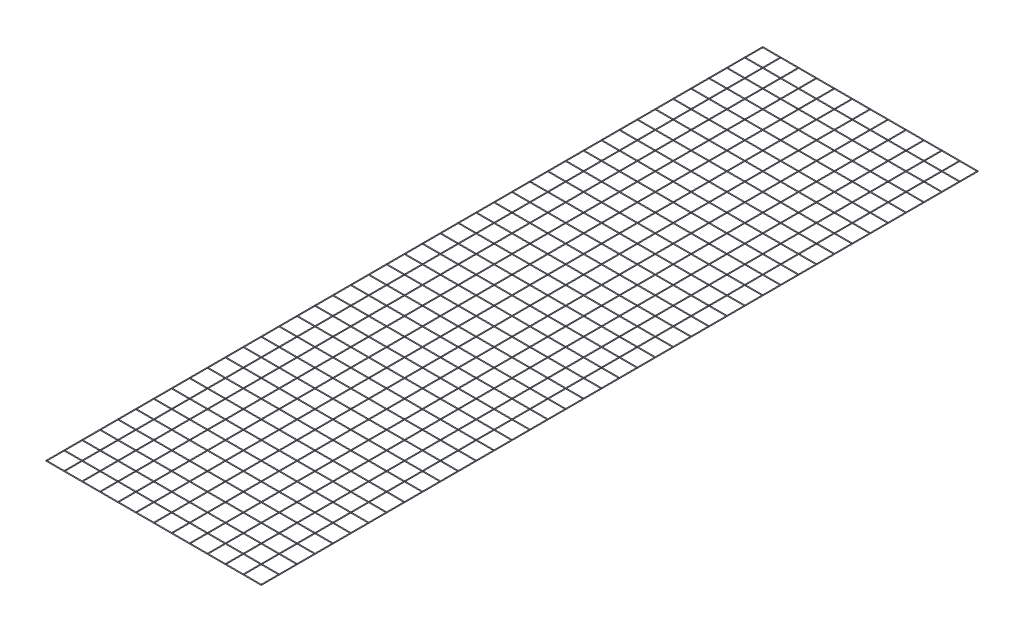
SolidWorks part; units mm, degrees
ref_plane "Piano frontale" through (0, 0, 0) normal (0, 0, 1) x (1, 0, 0)
ref_plane "Piano superiore" through (0, 0, 0) normal (0, 1, 0) x (1, 0, 0)
ref_plane "Piano destro" through (0, 0, 0) normal (1, 0, 0) x (0, 0, -1)
sketch "Schizzo1" plane through (0, 0, 0) normal (0, 0, 1) x (1, 0, 0)
  circle A0 centre (0, 0) radius 1
  circle A1 centre (50, 0) radius 1
  circle A2 centre (100, 0) radius 1
  circle A3 centre (150, 0) radius 1
  circle A4 centre (200, 0) radius 1
  circle A5 centre (250, 0) radius 1
  circle A6 centre (300, 0) radius 1
  circle A7 centre (350, 0) radius 1
  circle A8 centre (400, 0) radius 1
  circle A9 centre (450, 0) radius 1
  circle A10 centre (500, 0) radius 1
  circle A11 centre (550, 0) radius 1
  circle A12 centre (600, 0) radius 1
  circle A21 centre (950, 0) radius 1 [skipped]
  circle A22 centre (700, 0) radius 1 [skipped]
  circle A23 centre (750, 0) radius 1 [skipped]
  circle A24 centre (800, 0) radius 1 [skipped]
  circle A25 centre (850, 0) radius 1 [skipped]
  circle A26 centre (900, 0) radius 1 [skipped]
  circle A27 centre (650, 0) radius 1 [skipped]
  dimension "D1" = 2
  dimension "D2" = 20
extrude "Estrusione-Estrusione1" add sketch "Schizzo1" along normal blind 2000
sketch "Schizzo2" plane through (0, 0, 0) normal (1, 0, 0) x (0, 0, -1)
  circle A0 centre (0, 0) radius 1
  circle A1 centre (-50, 0) radius 1
  circle A2 centre (-100, 0) radius 1
  circle A3 centre (-150, 0) radius 1
  circle A4 centre (-200, 0) radius 1
  circle A5 centre (-250, 0) radius 1
  circle A6 centre (-300, 0) radius 1
  circle A7 centre (-350, 0) radius 1
  circle A8 centre (-400, 0) radius 1
  circle A9 centre (-450, 0) radius 1
  circle A10 centre (-500, 0) radius 1
  circle A11 centre (-550, 0) radius 1
  circle A12 centre (-600, 0) radius 1
  circle A13 centre (-650, 0) radius 1
  circle A14 centre (-700, 0) radius 1
  circle A15 centre (-750, 0) radius 1
  circle A16 centre (-800, 0) radius 1
  circle A17 centre (-850, 0) radius 1
  circle A18 centre (-900, 0) radius 1
  circle A19 centre (-950, 0) radius 1
  circle A20 centre (-1000, 0) radius 1
  circle A21 centre (-1050, 0) radius 1
  circle A22 centre (-1100, 0) radius 1
  circle A23 centre (-1150, 0) radius 1
  circle A24 centre (-1200, 0) radius 1
  circle A25 centre (-1250, 0) radius 1
  circle A26 centre (-1300, 0) radius 1
  circle A27 centre (-1350, 0) radius 1
  circle A28 centre (-1400, 0) radius 1
  circle A29 centre (-1450, 0) radius 1
  circle A30 centre (-1500, 0) radius 1
  circle A31 centre (-1550, 0) radius 1
  circle A32 centre (-1600, 0) radius 1
  circle A33 centre (-1650, 0) radius 1
  circle A34 centre (-1700, 0) radius 1
  circle A35 centre (-1750, 0) radius 1
  circle A36 centre (-1800, 0) radius 1
  circle A37 centre (-1850, 0) radius 1
  circle A38 centre (-1900, 0) radius 1
  circle A39 centre (-1950, 0) radius 1
  circle A40 centre (-2000, 0) radius 1
  dimension "D1" = 2
  dimension "D2" = 41
extrude "Estrusione-Estrusione2" add sketch "Schizzo2" along normal blind 600
